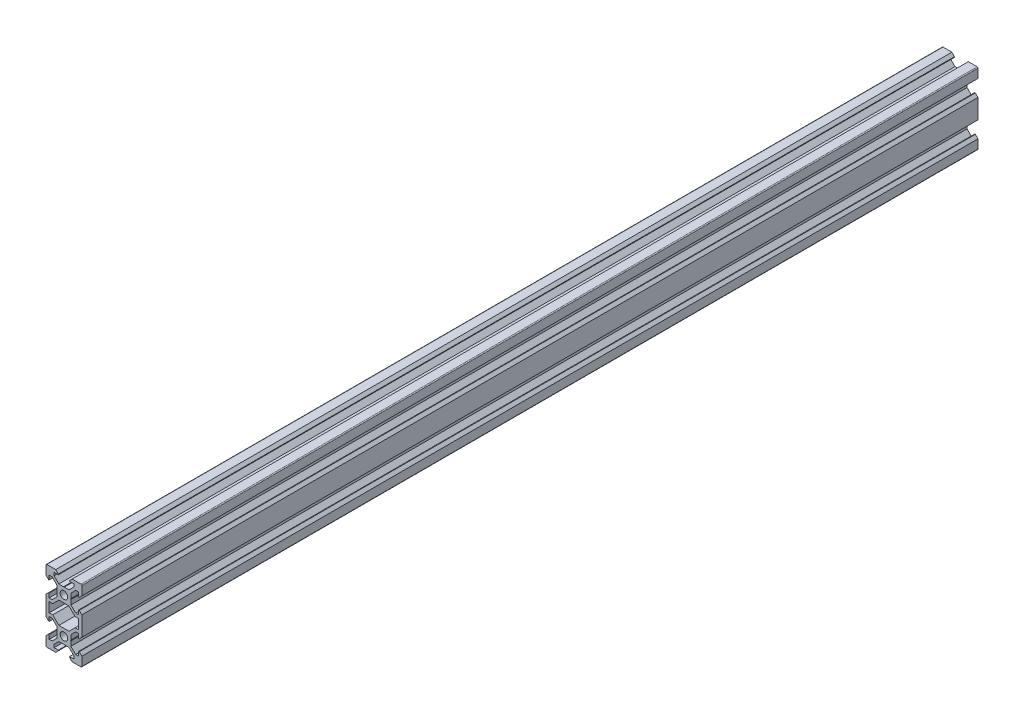
SolidWorks part; units mm, degrees
material "6061-T6 (SS)"
ref_plane "Front Plane" through (0, 0, 0) normal (0, 0, 1) x (1, 0, 0)
ref_plane "Top Plane" through (0, 0, 0) normal (0, 1, 0) x (1, 0, 0)
ref_plane "Right Plane" through (0, 0, 0) normal (1, 0, 0) x (0, 0, -1)
sketch "Sketch1" plane through (0, 0, 0) normal (0, 0, 1) x (1, 0, 0)
  line L0 (0, 0) -> (10, 0) construction
  line L1 (9.5, -20) -> (-9.5, -20)
  line L2 (10, -19.5) -> (10, 19.5)
  line L3 (9.5, 20) -> (-9.5, 20)
  line L4 (-10, -19.5) -> (-10, 19.5)
  line L5 (10, -20) -> (-10, 20) construction
  line L6 (10, 20) -> (-10, -20) construction
  circle A0 centre (0, 10) radius 2.1
  circle A1 centre (0, -10) radius 2.1
  arc A2 (-9.5, -20) -> (-10, -19.5) centre (-9.5, -19.5) cw
  arc A3 (9.5, -20) -> (10, -19.5) centre (9.5, -19.5) ccw
  arc A4 (10, 19.5) -> (9.5, 20) centre (9.5, 19.5) ccw
  arc A5 (-9.5, 20) -> (-10, 19.5) centre (-9.5, 19.5) ccw
  point P0 (0, 0)
  line B0 (0, 10) -> (0, 20) construction
  line B1 (0, 13.69) -> (-0.21, 13.9)
  line B2 (-0.21, 13.9) -> (-2.8393, 13.9)
  line B3 (-2.8393, 13.9) -> (-5.5, 16.5607)
  line B4 (-5.5, 16.5607) -> (-5.5, 18.2)
  line B5 (-5.5, 18.2) -> (-3.125, 18.2)
  line B6 (-3.125, 18.2) -> (-3.125, 18.545)
  line B7 (-3.125, 18.545) -> (-4.58, 20)
  line B8 (-4.58, 20) -> (4.58, 20)
  line B9 (0, 10) -> (-5.9132, 15.9132) construction
  line B10 (3.125, 18.545) -> (4.58, 20)
  line B11 (3.125, 18.2) -> (3.125, 18.545)
  line B12 (5.5, 18.2) -> (3.125, 18.2)
  line B13 (5.5, 16.5607) -> (5.5, 18.2)
  line B14 (2.8393, 13.9) -> (5.5, 16.5607)
  line B15 (0.21, 13.9) -> (2.8393, 13.9)
  line B16 (0, 13.69) -> (0.21, 13.9)
  line B17 (0, 10) -> (-10, 10) construction
  line B18 (-3.69, 10) -> (-3.9, 9.79)
  line B19 (-3.9, 9.79) -> (-3.9, 7.1607)
  line B20 (-3.9, 7.1607) -> (-6.5607, 4.5)
  line B21 (-6.5607, 4.5) -> (-8.2, 4.5)
  line B22 (-8.2, 4.5) -> (-8.2, 6.875)
  line B23 (-8.2, 6.875) -> (-8.545, 6.875)
  line B24 (-8.545, 6.875) -> (-10, 5.42)
  line B25 (-10, 5.42) -> (-10, 14.58)
  line B26 (0, 10) -> (-5.9132, 4.0868) construction
  line B27 (-8.545, 13.125) -> (-10, 14.58)
  line B28 (-8.2, 13.125) -> (-8.545, 13.125)
  line B29 (-8.2, 15.5) -> (-8.2, 13.125)
  line B30 (-6.5607, 15.5) -> (-8.2, 15.5)
  line B31 (-3.9, 12.8393) -> (-6.5607, 15.5)
  line B32 (-3.9, 10.21) -> (-3.9, 12.8393)
  line B33 (-3.69, 10) -> (-3.9, 10.21)
  line B34 (0, -10) -> (-10, -10) construction
  line B35 (-3.69, -10) -> (-3.9, -10.21)
  line B36 (-3.9, -10.21) -> (-3.9, -12.8393)
  line B37 (-3.9, -12.8393) -> (-6.5607, -15.5)
  line B38 (-6.5607, -15.5) -> (-8.2, -15.5)
  line B39 (-8.2, -15.5) -> (-8.2, -13.125)
  line B40 (-8.2, -13.125) -> (-8.545, -13.125)
  line B41 (-8.545, -13.125) -> (-10, -14.58)
  line B42 (-10, -14.58) -> (-10, -5.42)
  line B43 (0, -10) -> (-5.9132, -15.9132) construction
  line B44 (-8.545, -6.875) -> (-10, -5.42)
  line B45 (-8.2, -6.875) -> (-8.545, -6.875)
  line B46 (-8.2, -4.5) -> (-8.2, -6.875)
  line B47 (-6.5607, -4.5) -> (-8.2, -4.5)
  line B48 (-3.9, -7.1607) -> (-6.5607, -4.5)
  line B49 (-3.9, -9.79) -> (-3.9, -7.1607)
  line B50 (-3.69, -10) -> (-3.9, -9.79)
  line B51 (0, -10) -> (0, -20) construction
  line B52 (0, -13.69) -> (0.21, -13.9)
  line B53 (0.21, -13.9) -> (2.8393, -13.9)
  line B54 (2.8393, -13.9) -> (5.5, -16.5607)
  line B55 (5.5, -16.5607) -> (5.5, -18.2)
  line B56 (5.5, -18.2) -> (3.125, -18.2)
  line B57 (3.125, -18.2) -> (3.125, -18.545)
  line B58 (3.125, -18.545) -> (4.58, -20)
  line B59 (4.58, -20) -> (-4.58, -20)
  line B60 (0, -10) -> (5.9132, -15.9132) construction
  line B61 (-3.125, -18.545) -> (-4.58, -20)
  line B62 (-3.125, -18.2) -> (-3.125, -18.545)
  line B63 (-5.5, -18.2) -> (-3.125, -18.2)
  line B64 (-5.5, -16.5607) -> (-5.5, -18.2)
  line B65 (-2.8393, -13.9) -> (-5.5, -16.5607)
  line B66 (-0.21, -13.9) -> (-2.8393, -13.9)
  line B67 (0, -13.69) -> (-0.21, -13.9)
  line B68 (0, -10) -> (10, -10) construction
  line B69 (3.69, -10) -> (3.9, -9.79)
  line B70 (3.9, -9.79) -> (3.9, -7.1607)
  line B71 (3.9, -7.1607) -> (6.5607, -4.5)
  line B72 (6.5607, -4.5) -> (8.2, -4.5)
  line B73 (8.2, -4.5) -> (8.2, -6.875)
  line B74 (8.2, -6.875) -> (8.545, -6.875)
  line B75 (8.545, -6.875) -> (10, -5.42)
  line B76 (10, -5.42) -> (10, -14.58)
  line B77 (0, -10) -> (5.9132, -4.0868) construction
  line B78 (8.545, -13.125) -> (10, -14.58)
  line B79 (8.2, -13.125) -> (8.545, -13.125)
  line B80 (8.2, -15.5) -> (8.2, -13.125)
  line B81 (6.5607, -15.5) -> (8.2, -15.5)
  line B82 (3.9, -12.8393) -> (6.5607, -15.5)
  line B83 (3.9, -10.21) -> (3.9, -12.8393)
  line B84 (3.69, -10) -> (3.9, -10.21)
  line B85 (0, 10) -> (10, 10) construction
  line B86 (3.69, 10) -> (3.9, 10.21)
  line B87 (3.9, 10.21) -> (3.9, 12.8393)
  line B88 (3.9, 12.8393) -> (6.5607, 15.5)
  line B89 (6.5607, 15.5) -> (8.2, 15.5)
  line B90 (8.2, 15.5) -> (8.2, 13.125)
  line B91 (8.2, 13.125) -> (8.545, 13.125)
  line B92 (8.545, 13.125) -> (10, 14.58)
  line B93 (10, 14.58) -> (10, 5.42)
  line B94 (0, 10) -> (5.9132, 15.9132) construction
  line B95 (8.545, 6.875) -> (10, 5.42)
  line B96 (8.2, 6.875) -> (8.545, 6.875)
  line B97 (8.2, 4.5) -> (8.2, 6.875)
  line B98 (6.5607, 4.5) -> (8.2, 4.5)
  line B99 (3.9, 7.1607) -> (6.5607, 4.5)
  line B100 (3.9, 9.79) -> (3.9, 7.1607)
  line B101 (3.69, 10) -> (3.9, 9.79)
  line B102 (-8.2, -2.7) -> (-8.2, 2.7)
  line B103 (-8.2, 2.7) -> (-6.2393, 2.7)
  line B104 (-6.2393, 2.7) -> (-2.8393, 6.1)
  line B105 (-2.8393, 6.1) -> (2.8393, 6.1)
  line B106 (0, 6.1) -> (0, 0) construction
  line B107 (0, 0) -> (-8.2, 0) construction
  line B108 (6.2393, 2.7) -> (2.8393, 6.1)
  line B109 (8.2, 2.7) -> (6.2393, 2.7)
  line B110 (8.2, -2.7) -> (8.2, 2.7)
  line B111 (8.2, -2.7) -> (6.2393, -2.7)
  line B112 (6.2393, -2.7) -> (2.8393, -6.1)
  line B113 (-2.8393, -6.1) -> (2.8393, -6.1)
  line B114 (-6.2393, -2.7) -> (-2.8393, -6.1)
  line B115 (-8.2, -2.7) -> (-6.2393, -2.7)
  line B116 (0, 6.1) -> (0, 10) construction
  line B117 (0, 10) -> (-5.0927, 4.9073) construction
  dimension "D4" = 4.2
  dimension "D5" = 0.5
  dimension "D1" = 20
  dimension "D2" = 40
  dimension "D3" = 20
sketch_block_instance "V Slot 1-4"
sketch_block "V Slot 1" parameters "D1"=10, "D2"=11, "D3"=4.3, "D4"=1.8, "D5"=0.21, "D6"=45, "D7"=9.16, "D8"=1.5, "D9"=6.25
sketch_block_instance "V Slot 1-5"
sketch_block_instance "V Slot 1-6"
sketch_block_instance "V Slot 1-7"
sketch_block_instance "V Slot 1-8"
sketch_block_instance "V Slot 1-9"
sketch_block_instance "Center Cutout 1-1"
sketch_block "Center Cutout 1" parameters "D1"=5.4, "D2"=12.2, "D3"=8.2, "D4"=45, "D5"=10, "D6"=1.5
extrude "Boss-Extrude1" add sketch "Sketch1" along normal blind 500 contours B101 B86 B87 B88 B89 B90 B91 B92 L2 A4 L3 B10 B11 B12 B13 B14 B15 B16 B1 B2 B3 B4 B5 B6 B7 A5 L4 B27 B28 B29 B30 B31 B32 B33 B18 B19 B20 B21 B22 B23 B24 B44 B45 B46 B47 B48 B49 B50 B35 region at (7.04, -19.5528, 0)
